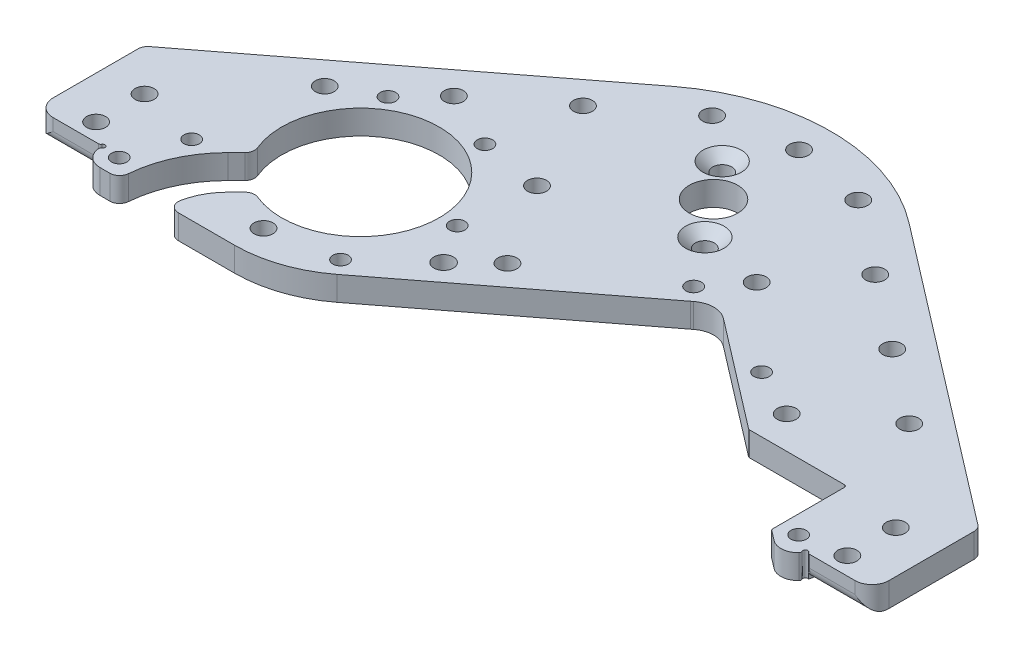
SolidWorks part; units mm, degrees
material "Alum Plate"
ref_plane "Front Plane" through (0, 0, 0) normal (0, 0, 1) x (1, 0, 0)
ref_plane "Top Plane" through (0, 0, 0) normal (0, 1, 0) x (1, 0, 0)
ref_plane "Right Plane" through (0, 0, 0) normal (1, 0, 0) x (0, 0, -1)
sketch "Top Layout" plane through (0, 0, 0) normal (0, 1, 0) x (1, 0, 0)
  line L0 (-114.046, -123.825) -> (-104.775, -123.825) construction
  line L1 (-104.775, -142.875) -> (-101.6, -142.875)
  line L2 (-104.775, -142.875) -> (-104.775, -104.775)
  line L3 (-104.775, -104.775) -> (-101.6, -104.775)
  line L4 (-101.6, -142.875) -> (-101.6, -104.775)
  line L5 (-104.775, -142.875) -> (-101.6, -104.775) construction
  line L6 (-104.775, -104.775) -> (-101.6, -142.875) construction
  line L7 (-19.05, -105.8164) -> (-101.6, -105.8164)
  line L8 (-19.05, -105.8164) -> (-19.05, -141.8336)
  line L9 (-19.05, -141.8336) -> (-101.6, -141.8336)
  line L10 (-101.6, -105.8164) -> (-101.6, -141.8336)
  line L11 (-19.05, -105.8164) -> (-101.6, -141.8336) construction
  line L12 (-19.05, -141.8336) -> (-101.6, -105.8164) construction
  line L13 (-133.096, -85.725) -> (-114.046, -85.725)
  line L14 (-133.096, -85.725) -> (-133.096, -161.925)
  line L15 (-133.096, -161.925) -> (-114.046, -161.925)
  line L16 (-114.046, -85.725) -> (-114.046, -161.925)
  line L17 (-133.096, -85.725) -> (-114.046, -161.925) construction
  line L18 (-133.096, -161.925) -> (-114.046, -85.725) construction
  line L19 (-104.775, -123.825) -> (0, -123.825) construction
  line L20 (0, -123.825) -> (0, 0) construction
  line L21 (-52.3528, -40.1717) -> (0, 0) construction
  line L22 (-70.6449, -16.3328) -> (-18.2922, 23.8388)
  line L23 (-34.0606, -64.0105) -> (18.2922, -23.8388)
  line L24 (-30.9251, 40.3023) -> (-122.2248, -29.7544)
  line L25 (-153.9748, -53.975) -> (-153.9748, -123.825)
  line L26 (-109.5248, -162.052) -> (109.5248, -162.052)
  line L27 (0, -162.052) -> (0, -123.825) construction
  line L28 (-109.5248, -162.052) -> (-109.5248, -20.0093) construction
  line L29 (-104.775, -142.875) -> (-104.775, -152.527)
  line L30 (-104.775, -152.527) -> (104.775, -152.527)
  line L31 (104.775, -104.775) -> (101.6, -104.775)
  line L32 (-144.4498, -73.025) -> (-109.5248, -73.025)
  line L33 (-144.4498, -73.025) -> (-144.4498, -123.825)
  line L34 (-144.4498, -123.825) -> (-109.5248, -123.825) construction
  line L35 (-109.5248, -73.025) -> (-109.5248, -162.052)
  line L36 (-144.4498, -73.025) -> (-109.5248, -123.825) construction
  line L37 (-144.4498, -123.825) -> (-109.5248, -73.025) construction
  line L38 (101.6, -142.875) -> (101.6, -104.775)
  line L39 (104.775, -142.875) -> (101.6, -142.875)
  line L40 (104.775, -142.875) -> (104.775, -104.775)
  line L41 (104.775, -142.875) -> (104.775, -152.527)
  line L42 (109.5248, -162.052) -> (109.5248, -20.0093) construction
  line L43 (30.9251, 40.3023) -> (122.2248, -29.7544)
  line L45 (19.05, -141.8336) -> (101.6, -141.8336)
  line L46 (101.6, -105.8164) -> (101.6, -141.8336)
  line L47 (19.05, -105.8164) -> (101.6, -105.8164)
  line L48 (19.05, -105.8164) -> (19.05, -141.8336)
  line L49 (133.096, -161.925) -> (114.046, -161.925)
  line L50 (114.046, -85.725) -> (114.046, -161.925)
  line L51 (133.096, -85.725) -> (114.046, -85.725)
  line L52 (133.096, -85.725) -> (133.096, -161.925)
  line L53 (144.4498, -123.825) -> (109.5248, -123.825) construction
  line L54 (109.5248, -73.025) -> (109.5248, -162.052)
  line L55 (144.4498, -73.025) -> (109.5248, -73.025)
  line L56 (144.4498, -73.025) -> (144.4498, -123.825)
  line L57 (-109.5248, -123.825) -> (-109.5248, -162.052) construction
  line L62 (-153.9748, -53.975) -> (-122.2248, -53.975)
  line L63 (-122.2248, -53.975) -> (-122.2248, -29.7544)
  line L64 (-144.4498, -123.825) -> (-153.9748, -123.825)
  line L65 (153.9748, -53.975) -> (153.9748, -123.825)
  line L66 (109.5248, -123.825) -> (109.5248, -162.052) construction
  line L67 (144.4498, -123.825) -> (153.9748, -123.825)
  line L68 (122.2248, -29.7544) -> (122.2248, -53.975)
  line L73 (-104.775, -104.775) -> (-104.775, -16.3647) construction
  line L74 (-95.25, -162.052) -> (-95.25, -9.0559) construction
  line L75 (-109.5248, -162.052) -> (-109.5248, -123.825) construction
  line L76 (109.5248, -162.052) -> (109.5248, -123.825) construction
  line L77 (122.2248, -53.975) -> (153.9748, -53.975)
  line L83 (104.775, -155.5496) -> (-104.775, -155.5496) construction
  line L88 (95.25, -162.052) -> (95.25, -9.0559) construction
  line L89 (104.775, -104.775) -> (104.775, -16.3647) construction
  line L92 (-104.775, -152.527) -> (-104.775, -162.052) construction
  line L93 (-14.605, -76.327) -> (14.605, -76.327)
  line L94 (-14.605, -76.327) -> (-14.605, -152.527)
  line L95 (-14.605, -152.527) -> (14.605, -152.527)
  line L96 (14.605, -76.327) -> (14.605, -152.527)
  line L97 (-14.605, -76.327) -> (14.605, -152.527) construction
  line L98 (-14.605, -152.527) -> (14.605, -76.327) construction
  line L99 (104.775, -152.527) -> (104.775, -162.052) construction
  line L100 (-19.05, -105.8164) -> (0, -105.8164) construction
  line L107 (0, -105.8164) -> (19.05, -105.8164) construction
  line L108 (104.775, -123.825) -> (114.046, -123.825) construction
  circle A0 centre (0, 0) radius 114.3
  circle A1 centre (0, 0) radius 6.35
  circle A2 centre (-52.3528, -40.1717) radius 17.8
  circle A3 centre (0, 0) radius 30.0482
  circle A4 centre (-52.3528, -40.1717) radius 30.0482
  arc A5 (-30.9251, 40.3023) -> (30.9251, 40.3023) centre (0, 0) cw
  point P2 (-103.1875, -123.825)
  point P7 (-60.325, -123.825)
  point P12 (-123.571, -123.825)
  point P30 (-126.9873, -98.425)
  point P35 (0, -114.427)
  point P53 (0, -152.527)
  dimension "D1" = 35.6
  dimension "D2" = 12.7
  dimension "D3" = 228.6
  dimension "D11" = 60.0964
  dimension "D12" = 50.8
  dimension "D14" = 52.5
  dimension "D4" = 3.175
  dimension "D5" = 19.05
  dimension "D6" = 76.2
  dimension "D7" = 82.55
  dimension "D8" = 38.1
  dimension "D9" = 104.775
  dimension "D10" = 18.0086
  dimension "D13" = 9.525
  dimension "D15" = 4.7498
  dimension "D16" = 9.525
  dimension "D17" = 9.652
  dimension "D18" = 50.8
  dimension "D19" = 12.446
  dimension "D20" = 65.9892
  dimension "D21" = 19.05
  dimension "D22" = 34.925
  dimension "D23" = 123.825
  dimension "D24" = 12.7
  dimension "D25" = 9.525
  dimension "D26" = 29.21
  dimension "D27" = 76.2
  dimension "D28" = 3.0226
sketch "Side Layout" plane through (0, 0, 0) normal (1, 0, 0) x (0, 0, -1)
  line L0 (0, -38.1) -> (0, 33.7344) construction
  line L1 (-114.3, -20.955) -> (114.3, -20.955)
  line L2 (-114.3, -20.955) -> (-114.3, -33.655)
  line L3 (-114.3, -33.655) -> (114.3, -33.655)
  line L4 (114.3, -20.955) -> (114.3, -33.655)
  line L5 (-114.3, -20.955) -> (114.3, -33.655) construction
  line L6 (-114.3, -33.655) -> (114.3, -20.955) construction
  line L7 (-9.525, -32.9406) -> (9.525, -32.9406)
  line L8 (-9.525, -32.9406) -> (-9.525, -38.1)
  line L9 (-9.525, -38.1) -> (9.525, -38.1)
  line L10 (9.525, -32.9406) -> (9.525, -38.1)
  line L11 (-9.525, -32.9406) -> (9.525, -38.1) construction
  line L12 (-9.525, -38.1) -> (9.525, -32.9406) construction
  line L13 (-11.9126, -29.3338) -> (11.9126, -29.3338)
  line L14 (-11.9126, -29.3338) -> (-11.9126, -32.9406)
  line L15 (-11.9126, -32.9406) -> (11.9126, -32.9406)
  line L16 (11.9126, -29.3338) -> (11.9126, -32.9406)
  line L17 (-11.9126, -29.3338) -> (11.9126, -32.9406) construction
  line L18 (-11.9126, -32.9406) -> (11.9126, -29.3338) construction
  line L19 (-6.35, -32.9406) -> (6.35, -32.9406)
  line L20 (-6.35, -32.9406) -> (-6.35, 33.7344)
  line L21 (-6.35, 33.7344) -> (6.35, 33.7344)
  line L22 (6.35, -32.9406) -> (6.35, 33.7344)
  line L23 (-6.35, -32.9406) -> (6.35, 33.7344) construction
  line L24 (-6.35, 33.7344) -> (6.35, -32.9406) construction
  line L25 (-162.052, 0) -> (-123.825, 0) construction
  line L26 (114.3, -33.655) -> (114.3, 0) construction
  line L27 (-142.875, 19.05) -> (-104.775, 19.05)
  line L28 (-40.1717, -9.525) -> (-40.1717, 5.4) construction
  line L29 (-142.875, 19.05) -> (-142.875, -19.05)
  line L30 (-142.875, -19.05) -> (-104.775, -19.05)
  line L31 (-104.775, 19.05) -> (-104.775, -19.05)
  line L32 (-142.875, 19.05) -> (-104.775, -19.05) construction
  line L33 (-142.875, -19.05) -> (-104.775, 19.05) construction
  line L34 (-130.175, -38.1) -> (-117.9516, -38.1) construction
  line L35 (-57.9717, -14.6) -> (-22.3717, -14.6)
  line L36 (-30.0482, -2.794) -> (30.0482, -2.794)
  line L37 (-30.0482, -2.794) -> (-30.0482, -20.955)
  line L38 (-30.0482, -20.955) -> (30.0482, -20.955)
  line L39 (30.0482, -2.794) -> (30.0482, -20.955)
  line L40 (-30.0482, -2.794) -> (30.0482, -20.955) construction
  line L41 (-30.0482, -20.955) -> (30.0482, -2.794) construction
  line L42 (-30.0482, -2.794) -> (-30.0482, 0) construction
  line L43 (-123.825, 0) -> (0, 0) construction
  line L44 (-57.9717, -14.6) -> (-57.9717, 25.4)
  line L45 (-57.9717, 25.4) -> (-22.3717, 25.4)
  line L46 (-22.3717, -14.6) -> (-22.3717, 25.4)
  line L47 (-19.05, 0) -> (19.05, 0)
  line L48 (-19.05, 0) -> (-19.05, -1.9812)
  line L49 (-19.05, -1.9812) -> (19.05, -1.9812)
  line L50 (19.05, 0) -> (19.05, -1.9812)
  line L51 (-19.05, 0) -> (19.05, -1.9812) construction
  line L52 (-19.05, -1.9812) -> (19.05, 0) construction
  line L53 (-70.2199, -3.175) -> (-10.1235, -3.175)
  line L54 (-70.2199, -3.175) -> (-70.2199, -15.875)
  line L55 (-70.2199, -15.875) -> (-10.1235, -15.875)
  line L56 (-10.1235, -3.175) -> (-10.1235, -15.875)
  line L57 (-70.2199, -3.175) -> (-10.1235, -15.875) construction
  line L58 (-70.2199, -15.875) -> (-10.1235, -3.175) construction
  line L59 (-40.1717, -9.525) -> (-40.1717, 0) construction
  line L60 (-57.9717, -14.6) -> (-22.3717, 25.4) construction
  line L61 (-57.9717, 25.4) -> (-22.3717, -14.6) construction
  line L62 (-22.3717, 0) -> (-57.9717, 0) construction
  line L63 (-137.8162, 0) -> (-123.825, -13.9912) construction
  line L64 (-139.065, 15.24) -> (-108.585, 15.24) construction
  line L65 (-139.065, 15.24) -> (-139.065, -15.24) construction
  line L66 (-139.065, -15.24) -> (-108.585, -15.24) construction
  line L67 (-108.585, 15.24) -> (-108.585, -15.24) construction
  line L68 (-139.065, 15.24) -> (-108.585, -15.24) construction
  line L69 (-139.065, -15.24) -> (-108.585, 15.24) construction
  line L70 (-137.8162, 0) -> (-123.825, 13.9912) construction
  line L71 (-123.825, -13.9912) -> (-109.8338, 0) construction
  line L72 (-123.825, 13.9912) -> (-109.8338, 0) construction
  line L73 (-137.8162, 0) -> (-109.8338, 0) construction
  line L74 (-123.825, -13.9912) -> (-123.825, 13.9912) construction
  line L75 (-6.35, 17.8594) -> (6.35, 17.8594)
  line L76 (114.3, 0) -> (-114.3, 0) construction
  line L77 (-22.3717, 19.05) -> (-6.35, 19.05) construction
  line L78 (-123.825, 38.1) -> (-97.9206, 38.1) construction
  line L79 (-19.05, -3.5814) -> (19.05, -3.5814)
  line L80 (-19.05, -3.5814) -> (-19.05, -1.9812)
  line L81 (-19.05, -1.9812) -> (19.05, -1.9812)
  line L82 (19.05, -3.5814) -> (19.05, -1.9812)
  line L83 (-19.05, -3.5814) -> (19.05, -1.9812) construction
  line L84 (-19.05, -1.9812) -> (19.05, -3.5814) construction
  line L85 (-8.7376, -16.7608) -> (8.7376, -16.7608)
  line L86 (-8.7376, -16.7608) -> (-8.7376, -29.3338)
  line L87 (-8.7376, -29.3338) -> (8.7376, -29.3338)
  line L88 (8.7376, -16.7608) -> (8.7376, -29.3338)
  line L89 (-8.7376, -16.7608) -> (8.7376, -29.3338) construction
  line L90 (-8.7376, -29.3338) -> (8.7376, -16.7608) construction
  line L91 (-8.7376, -3.5814) -> (8.7376, -3.5814)
  line L92 (-8.7376, -3.5814) -> (-8.7376, -16.1544)
  line L93 (-8.7376, -16.1544) -> (8.7376, -16.1544)
  line L94 (8.7376, -3.5814) -> (8.7376, -16.1544)
  line L95 (-8.7376, -3.5814) -> (8.7376, -16.1544) construction
  line L96 (-8.7376, -16.1544) -> (8.7376, -3.5814) construction
  circle A0 centre (-123.825, 0) radius 18.0086
  circle A1 centre (-123.825, 0) radius 38.1
  circle A2 centre (-139.065, 15.24) radius 1.905
  circle A3 centre (-108.585, 15.24) radius 1.905
  circle A4 centre (-108.585, -15.24) radius 1.905
  circle A5 centre (-139.065, -15.24) radius 1.905
  circle A6 centre (-137.8162, 0) radius 1.6002
  circle A7 centre (-123.825, 13.9912) radius 1.6002
  circle A8 centre (-109.8338, 0) radius 1.6002
  circle A9 centre (-123.825, -13.9912) radius 1.6002
  point P0 (0, -27.305)
  point P6 (0, -31.1372)
  point P7 (0, -35.5203)
  point P21 (0, 0.3969)
  point P32 (0, -11.8745)
  point P43 (0, -0.9906)
  point P55 (-40.1717, -9.525)
  point P72 (-40.1717, 5.4)
  point P88 (0, -23.0473)
  point P93 (0, -2.7813)
  point P102 (0, -9.8679)
  dimension "D17" = 3.81
  dimension "D18" = 3.2004
  dimension "D1" = 12.7
  dimension "D2" = 5.1594
  dimension "D3" = 19.05
  dimension "D4" = 3.6068
  dimension "D5" = 23.8252
  dimension "D6" = 12.7
  dimension "D7" = 18.161
  dimension "D8" = 1.9812
  dimension "D9" = 12.7
  dimension "D10" = 40
  dimension "D11" = 25.4
  dimension "D12" = 50.8
  dimension "D13" = 41.275
  dimension "D14" = 30.48
  dimension "D15" = 4.445
  dimension "D16" = 19.7866
  dimension "D19" = 15.875
  dimension "D20" = 6.35
  dimension "D21" = 38.1
  dimension "D22" = 1.6002
  dimension "D23" = 38.1
  dimension "D24" = 17.4752
  dimension "D25" = 12.573
ref_plane "Plane1" through (0, 25.4, 0) normal (0, 1, 0) x (1, 0, 0)
sketch "Sketch3" plane through (0, 25.4, 0) normal (0, 1, 0) x (1, 0, 0)
  line L0 (-104.775, -36.3747) -> (-30.9251, 20.2924)
  line L1 (-104.775, -104.775) -> (-104.775, -16.3647) construction
  line L2 (0, -200130.175) -> (0, 199882.0484) construction
  line L3 (-30.9251, 40.3023) -> (-122.2248, -29.7544) construction
  line L5 (-104.775, -36.3747) -> (-104.775, -77.6497)
  line L6 (-92.075, -77.6497) -> (-104.775, -77.6497)
  line L7 (30.9251, 20.2924) -> (104.775, -36.3747)
  line L8 (104.775, -77.6497) -> (92.075, -77.6497)
  line L9 (104.775, -36.3747) -> (104.775, -77.6497)
  line L11 (104.775, -104.775) -> (104.775, -16.3647) construction
  line L12 (30.9251, 40.3023) -> (122.2248, -29.7544) construction
  line L13 (92.075, -74.6536) -> (24.1423, -22.5271)
  line L14 (-32.2514, -66.3682) -> (20.1013, -26.1965)
  line L15 (-30.9251, 20.2924) -> (0, 44.022)
  line L16 (0, 44.022) -> (30.9251, 20.2924)
  line L17 (-92.075, -77.6497) -> (-92.075, -73.1917)
  line L19 (-92.075, -73.1917) -> (-52.3528, -73.1917)
  line L20 (92.075, -74.6536) -> (92.075, -77.6497)
  circle A1 centre (-52.3528, -40.1717) radius 20.6375
  circle A2 centre (0, 0) radius 6.35
  circle A3 centre (0, 0) radius 6.35 construction
  arc A4 (-52.3528, -73.1917) -> (-32.2514, -66.3682) centre (-52.3528, -40.1717) ccw
  arc A5 (20.1013, -26.1965) -> (24.1423, -22.5271) centre (0, 0) ccw
  arc A6 (30.9251, 20.2924) -> (-30.9251, 20.2924) centre (0, -20.01) ccw construction
  point P28 (0, 44.022)
  dimension "D1" = 33.02
  dimension "D5" = 50.8
  dimension "D7" = 41.275
  dimension "D2" = 41.275
  dimension "D3" = 34.925
  dimension "D4" = 12.7
  dimension "D6" = 38.1
extrude "Boss-Extrude1" add sketch "Sketch3" against normal blind 6.35
ref_plane "Plane3" through (-104.775, 0, 0) normal (-1, 0, 0) x (0, 0, 1)
sketch "Sketch6" plane through (-104.775, 0, 0) normal (-1, 0, 0) x (0, 0, 1)
  line L0 (162.052, -25.4) -> (162.052, 25.4)
  line L1 (162.052, 25.4) -> (77.6497, 25.4)
  line L2 (36.3747, 25.4) -> (77.6497, 25.4) construction
  line L3 (147.7645, 11.1125) -> (162.052, 11.1125) construction
  line L4 (162.052, 0) -> (71.2997, 0) construction
  line L5 (77.6497, 25.4) -> (77.6497, 19.05)
  line L6 (77.6497, 19.05) -> (36.3747, 19.05)
  line L7 (36.3747, 19.05) -> (36.3747, 6.35)
  line L8 (36.3747, 6.35) -> (71.2997, 6.35)
  line L10 (99.6315, -3.175) -> (99.6315, 11.1125) construction
  line L11 (71.2997, -25.4) -> (162.052, -25.4)
  line L13 (71.2997, 6.35) -> (71.2997, -25.4)
  line L14 (152.527, -25.4) -> (152.527, 25.4) construction
  line L15 (99.6315, 11.1125) -> (99.6315, 25.4) construction
  line L16 (147.7645, 11.1125) -> (147.7645, 25.4) construction
  line L17 (94.869, -7.9375) -> (104.394, -7.9375) construction
  line L18 (94.869, -7.9375) -> (94.869, 25.4) construction
  line L19 (94.869, 25.4) -> (104.394, 25.4) construction
  line L20 (104.394, -7.9375) -> (104.394, 25.4) construction
  line L21 (94.869, -7.9375) -> (104.394, 25.4) construction
  line L22 (94.869, 25.4) -> (104.394, -7.9375) construction
  line L23 (147.7645, 11.1125) -> (147.7645, -3.175) construction
  line L24 (104.394, -7.9375) -> (123.825, -7.9375) construction
  line L25 (143.002, -7.9375) -> (152.527, -7.9375) construction
  line L26 (143.002, -7.9375) -> (143.002, 25.4) construction
  line L27 (143.002, 25.4) -> (152.527, 25.4) construction
  line L28 (152.527, -7.9375) -> (152.527, 25.4) construction
  line L29 (143.002, -7.9375) -> (152.527, 25.4) construction
  line L30 (143.002, 25.4) -> (152.527, -7.9375) construction
  line L31 (123.825, -7.9375) -> (152.527, -7.9375) construction
  line L32 (104.775, 19.05) -> (104.775, -19.05) construction
  line L34 (155.702, -25.4) -> (155.702, 25.4) construction
  circle A0 centre (109.8338, 0) radius 1.6002 construction
  circle A1 centre (123.825, 13.9912) radius 1.6002 construction
  circle A2 centre (137.8162, 0) radius 1.6002 construction
  circle A3 centre (123.825, -13.9912) radius 1.6002 construction
  circle A4 centre (109.8338, 0) radius 1.6002 construction
  circle A5 centre (123.825, 13.9912) radius 1.6002 construction
  circle A6 centre (137.8162, 0) radius 1.6002 construction
  circle A7 centre (123.825, -13.9912) radius 1.6002 construction
  circle A8 centre (123.825, 0) radius 18.0086 construction
  circle A9 centre (123.825, 0) radius 18.0086 construction
  circle A10 centre (123.825, 0) radius 9.525
  circle A11 centre (108.585, -15.24) radius 1.905 construction
  circle A12 centre (108.585, 15.24) radius 1.905 construction
  circle A13 centre (139.065, 15.24) radius 1.905 construction
  circle A14 centre (139.065, -15.24) radius 1.905 construction
  circle A15 centre (108.585, -15.24) radius 1.905
  circle A16 centre (108.585, 15.24) radius 1.905
  circle A17 centre (139.065, 15.24) radius 1.905
  circle A18 centre (139.065, -15.24) radius 1.905
  circle A19 centre (147.7645, 11.1125) radius 2.5527
  circle A26 centre (99.6315, 11.1125) radius 2.5527
  circle A27 centre (99.6315, -3.175) radius 2.5527
  circle A28 centre (147.7645, -3.175) radius 2.5527
  point P29 (0, 0)
  point P55 (99.6315, 8.7312)
  point P61 (147.7645, 8.7312)
  dimension "D4" = 19.05
  dimension "D7" = 5.1054
  dimension "D1" = 6.35
  dimension "D2" = 12.7
  dimension "D3" = 25.4
  dimension "D5" = 6.35
  dimension "D6" = 3.175
  dimension "D8" = 0.381
  dimension "D9" = 14.2875
  dimension "D10" = 9.525
  dimension "D12" = 33.3375
sketch "Sketch12" [suppressed] plane through (0, 19.05, 0) normal (0, 1, 0) x (1, 0, 0)
  line L0 (-104.775, -77.6497) -> (-104.775, -36.3747)
  line L1 (-104.775, -36.3747) -> (-92.075, -36.3747)
  line L3 (-92.075, -36.3747) -> (-92.075, -77.6497)
  line L5 (-92.075, -77.6497) -> (-104.775, -77.6497)
  line L6 (-98.425, -77.6497) -> (-98.425, -63.3622) construction
  line L7 (-98.425, -63.3622) -> (-98.425, -50.6622) construction
  line L8 (-98.425, -50.6622) -> (-98.425, -36.3747) construction
  line L10 (-98.425, -36.3747) -> (-104.775, -36.3747) construction
  circle A0 centre (-98.425, -63.3622) radius 2.5527
  circle A1 centre (-98.425, -50.6622) radius 2.5527
  dimension "D2" = 5.1054
  dimension "D1" = 12.7
  dimension "D3" = 12.7
sketch "Sketch8" plane through (0, 25.4, 0) normal (0, 1, 0) x (1, 0, 0)
  line L0 (-109.5248, -162.052) -> (-109.5248, -20.0093) construction
  line L1 (-104.775, -77.6497) -> (-109.5248, -77.6497)
  line L2 (-104.775, -77.6497) -> (-104.775, -36.3747)
  line L3 (-104.775, -36.3747) -> (-109.5248, -36.3747)
  line L4 (-109.5248, -77.6497) -> (-109.5248, -36.3747)
  line L5 (-104.775, -77.6497) -> (-109.5248, -36.3747) construction
  line L6 (-104.775, -36.3747) -> (-109.5248, -77.6497) construction
  line L7 (104.775, -77.6497) -> (109.5248, -77.6497)
  line L8 (104.775, -77.6497) -> (104.775, -36.3747)
  line L9 (104.775, -36.3747) -> (109.5248, -36.3747)
  line L10 (109.5248, -77.6497) -> (109.5248, -36.3747)
  line L11 (104.775, -77.6497) -> (109.5248, -36.3747) construction
  line L12 (104.775, -36.3747) -> (109.5248, -77.6497) construction
  point P4 (-107.1499, -57.0122)
  point P10 (107.1499, -57.0122)
extrude "Boss-Extrude4" add sketch "Sketch8" against normal through all
sketch "Sketch9" plane through (0, 25.4, 0) normal (0, 1, 0) x (1, 0, 0)
  line L0 (7.4916, -9.7632) -> (0, 0) construction
  line L1 (0, 0) -> (-7.4916, 9.7632) construction
  line L2 (0, 44.022) -> (-104.775, -36.3747) construction
  circle A0 centre (-7.4916, 9.7632) radius 2.4892
  circle A1 centre (7.4916, -9.7632) radius 2.4892
  dimension "D2" = 4.9784
  dimension "D1" = 24.6126
extrude "Collar Holes" cut sketch "Sketch9" against normal through all
sketch "Sketch10" plane through (0, 25.4, 0) normal (0, 1, 0) x (1, 0, 0)
  line L0 (0, 33.4567) -> (0, 30.79) construction
  line L1 (-5.1026, 40.1066) -> (0, 33.4567) construction
  line L2 (0, 33.4567) -> (5.1026, 40.1066) construction
  line L3 (0, 44.022) -> (-104.775, -36.3747) construction
  line L4 (104.775, -36.3747) -> (0, 44.022) construction
  circle A0 centre (0, 33.4567) radius 4.7625 construction
  circle A1 centre (0, 33.4567) radius 2.0193
  arc A3 (30.9251, 20.2924) -> (-30.9251, 20.2924) centre (0, -20.01) ccw construction
  dimension "D2" = 9.525
  dimension "D3" = 4.0386
  dimension "D1" = 8.382
extrude "Spacer Holes" cut sketch "Sketch10" against normal through all
pattern_linear "Spacer Hole Pattern" count 5 spacing 24.13 along (-0.7934, 0, 0.6088) of "Spacer Holes"
mirror "Spacer Hole Mirror" about plane through (0, 0, 0) normal (1, 0, 0) of "Spacer Hole Pattern"
sketch "Sketch16" plane through (0, 25.4, 0) normal (0, 1, 0) x (1, 0, 0)
  line L0 (-109.5248, -50.6622) -> (-98.425, -50.6622) construction
  line L1 (-109.5248, -36.3747) -> (-109.5248, -77.6497) construction
  line L2 (-98.425, -50.6622) -> (-98.425, -63.3622) construction
  line L3 (-98.425, -63.3622) -> (-109.5248, -63.3622) construction
  line L4 (-98.425, -63.3622) -> (-98.425, -77.6497) construction
  line L5 (-109.5248, -77.6497) -> (-92.075, -77.6497) construction
  line L6 (-98.425, -50.6622) -> (-98.425, -36.3747) construction
  line L7 (-104.775, -36.3747) -> (-109.5248, -36.3747) construction
  line L8 (-104.775, -36.3747) -> (-104.775, -77.6497) construction
  line L9 (0, 0) -> (0, 30.79) construction
  line L10 (104.775, -36.3747) -> (104.775, -77.6497) construction
  circle A0 centre (-98.425, -50.6622) radius 2.0193
  circle A1 centre (-98.425, -63.3622) radius 2.0193
  circle A4 centre (98.425, -63.3622) radius 2.0193
  circle A5 centre (98.425, -50.6622) radius 2.0193
  arc A6 (30.9251, 20.2924) -> (-30.9251, 20.2924) centre (0, -20.01) ccw construction
  dimension "D1" = 4.0386
  dimension "D2" = 12.7
  dimension "D3" = 6.35
extrude "Custom Nutstrip Holes" cut sketch "Sketch16" against normal through all
sketch "Sketch36" plane through (0, 25.4, 0) normal (0, 1, 0) x (1, 0, 0)
  line L0 (-52.3528, -65.5717) -> (-12.44, -41.5615) construction
  line L1 (-12.44, -41.5615) -> (24.5129, -13.2066) construction
  line L2 (24.5129, -13.2066) -> (58.2939, -39.1277) construction
  line L3 (-32.2514, -66.3682) -> (20.1013, -26.1965) construction
  line L4 (24.1423, -22.5271) -> (92.075, -74.6536) construction
  line L5 (-12.44, -41.5615) -> (-7.8012, -47.6069) construction
  line L6 (58.2939, -39.1277) -> (53.6552, -45.1731) construction
  line L7 (-52.3528, -65.5717) -> (-52.3528, -40.1717) construction
  line L8 (58.2939, -39.1277) -> (92.075, -65.0488) construction
  line L9 (92.075, -65.0488) -> (92.075, -77.6497) construction
  line L10 (-52.3528, -40.1717) -> (-26.1764, -20.0858) construction
  line L11 (-26.1764, -20.0858) -> (0, 0) construction
  line L12 (92.075, -74.6536) -> (92.075, -77.6497) construction
  circle A0 centre (-52.3528, -65.5717) radius 2.0193
  circle A1 centre (58.2939, -39.1277) radius 2.0193
  circle A2 centre (24.5129, -13.2066) radius 2.0193
  circle A3 centre (-12.44, -41.5615) radius 2.0193
  circle A4 centre (-76.5745, -25.3009) radius 2.0193 construction
  circle A5 centre (-52.3528, -65.5717) radius 4.7625 construction
  circle A6 centre (-12.44, -41.5615) radius 4.7625 construction
  circle A7 centre (24.5129, -13.2066) radius 4.7625 construction
  circle A8 centre (58.2939, -39.1277) radius 4.7625 construction
  arc A9 (-52.3528, -73.1917) -> (-32.2514, -66.3682) centre (-52.3528, -40.1717) ccw construction
  circle A10 centre (-26.1764, -20.0858) radius 2.0193
  dimension "D1" = 9.525
  dimension "D2" = 25.4
  dimension "D3" = 7.62
extrude "Aux Spacer Holes" cut sketch "Sketch36" against normal through all
sketch "Sketch38" [suppressed] plane through (-104.775, 0, 0) normal (-1, 0, 0) x (0, 0, 1)
  line L1 (152.527, -7.9375) -> (143.002, -7.9375)
  line L2 (152.527, -7.9375) -> (152.527, 25.4)
  line L3 (152.527, 25.4) -> (143.002, 25.4)
  line L4 (143.002, -7.9375) -> (143.002, 25.4)
  line L5 (152.527, -7.9375) -> (143.002, 25.4) construction
  line L6 (152.527, 25.4) -> (143.002, -7.9375) construction
  point P4 (147.7645, 8.7312)
extrude "Cut-Extrude16" [suppressed] cut sketch "Sketch38" against normal blind 9.525
sketch "Sketch46" [suppressed] plane through (-104.775, 0, 0) normal (-1, 0, 0) x (0, 0, 1)
  line L0 (142.875, 19.05) -> (104.775, -19.05) construction
  line L1 (104.14, 19.685) -> (143.51, 19.685)
  line L2 (104.14, 19.685) -> (104.14, -19.685)
  line L3 (104.14, -19.685) -> (143.51, -19.685)
  line L4 (143.51, 19.685) -> (143.51, -19.685)
  line L5 (104.14, 19.685) -> (143.51, -19.685) construction
  line L6 (104.14, -19.685) -> (143.51, 19.685) construction
  point P0 (123.825, 0)
  dimension "D1" = 39.37
extrude "Cut-Extrude21" [suppressed] cut sketch "Sketch46" against normal blind 6.985
ref_plane "Plane5" through (0, 0, 152.527) normal (0, 0, 1) x (1, 0, 0)
sketch "Sketch41" plane through (0, 0, 152.527) normal (0, 0, 1) x (1, 0, 0)
  line L0 (-104.775, -7.9375) -> (-104.775, 25.4) construction
  line L1 (-104.775, -7.9375) -> (-104.775, 12.7)
  line L2 (-104.775, -7.9375) -> (104.775, -7.9375)
  line L3 (104.775, -7.9375) -> (104.775, 12.7)
  line L4 (104.775, 25.4) -> (-104.775, 25.4)
  line L5 (0, -7.9375) -> (0, 25.4) construction
  line L6 (-104.775, 3.9624) -> (-100.0125, 3.9624) construction
  line L7 (-100.0125, 3.9624) -> (-100.0125, 25.4) construction
  line L8 (104.775, 3.9624) -> (100.0125, 3.9624) construction
  line L9 (100.0125, 3.9624) -> (100.0125, 25.4) construction
  line L10 (19.05, 20.6375) -> (23.8252, 20.6375) construction
  line L11 (19.05, 15.875) -> (78.5876, 15.875) construction
  line L12 (19.05, 15.875) -> (19.05, 25.4) construction
  line L13 (19.05, 25.4) -> (78.5876, 25.4) construction
  line L14 (78.5876, 15.875) -> (78.5876, 25.4) construction
  line L15 (19.05, 15.875) -> (78.5876, 25.4) construction
  line L16 (19.05, 25.4) -> (78.5876, 15.875) construction
  line L17 (23.8252, 20.6375) -> (38.1127, 20.6375) construction
  line L18 (38.1127, 20.6375) -> (52.4002, 20.6375) construction
  line L19 (52.4002, 20.6375) -> (66.6877, 20.6375) construction
  line L20 (-104.775, 25.4) -> (-112.395, 25.4)
  line L21 (-112.395, 25.4) -> (-112.395, 3.175)
  line L22 (-112.395, 3.175) -> (-109.5248, 3.175)
  line L23 (-109.5248, 3.175) -> (-109.5248, 12.7)
  line L24 (-109.5248, 12.7) -> (-104.775, 12.7)
  line L25 (-104.775, 12.7) -> (-104.775, 25.4) construction
  line L26 (104.775, 25.4) -> (112.395, 25.4)
  line L27 (112.395, 25.4) -> (112.395, 3.175)
  line L28 (112.395, 3.175) -> (109.5248, 3.175)
  line L29 (109.5248, 3.175) -> (109.5248, 12.7)
  line L30 (109.5248, 12.7) -> (104.775, 12.7)
  line L31 (104.775, 12.7) -> (104.775, 25.4) construction
  line L32 (-100.0125, 3.9624) -> (-87.3125, 3.9624) construction
  line L33 (-63.5, -1.5875) -> (0, -1.5875) construction
  line L34 (0, -1.5875) -> (63.5, -1.5875) construction
  line L35 (63.5, -1.5875) -> (63.5, -7.9375) construction
  circle A0 centre (-100.0125, 3.9624) radius 2.5527
  circle A1 centre (100.0125, 3.9624) radius 2.5527
  circle A2 centre (23.8252, 20.6375) radius 2.5527
  circle A3 centre (38.1127, 20.6375) radius 2.5527
  circle A4 centre (52.4002, 20.6375) radius 2.5527
  circle A5 centre (66.6877, 20.6375) radius 2.5527
  circle A6 centre (-66.6877, 20.6375) radius 2.5527
  circle A7 centre (-52.4002, 20.6375) radius 2.5527
  circle A8 centre (-38.1127, 20.6375) radius 2.5527
  circle A9 centre (-23.8252, 20.6375) radius 2.5527
  circle A10 centre (-87.3125, 3.9624) radius 2.5527
  circle A11 centre (87.3125, 3.9624) radius 2.5527
  circle A12 centre (-63.5, -1.5875) radius 2.5527
  circle A13 centre (63.5, -1.5875) radius 2.5527
  point P14 (48.8188, 20.6375)
  dimension "D3" = 5.1054
  dimension "D7" = 5.1054
  dimension "D1" = 21.4376
  dimension "D2" = 4.7625
  dimension "D4" = 9.525
  dimension "D5" = 59.5376
  dimension "D6" = 4.7752
  dimension "D8" = 14.2875
  dimension "D9" = 7.62
  dimension "D10" = 4.7498
  dimension "D11" = 12.7
  dimension "D12" = 9.525
  dimension "D13" = 19.05
  dimension "D14" = 12.7
  dimension "D15" = 6.35
  dimension "D16" = 63.5
sketch "Sketch43" [suppressed] plane through (-109.5248, 0, 0) normal (-1, 0, 0) x (0, 0, 1)
  line L1 (152.527, 12.7) -> (155.702, 12.7)
  line L2 (152.527, 12.7) -> (152.527, 25.4)
  line L3 (152.527, 25.4) -> (155.702, 25.4)
  line L4 (155.702, 12.7) -> (155.702, 25.4)
  line L5 (152.527, 12.7) -> (155.702, 25.4) construction
  line L6 (152.527, 25.4) -> (155.702, 12.7) construction
  line L7 (162.052, 25.4) -> (77.6497, 25.4) construction
  point P4 (154.1145, 19.05)
  dimension "D1" = 3.175
sketch "Sketch44" plane through (0, 25.4, 0) normal (0, 1, 0) x (1, 0, 0)
  line L0 (73.8315, -147.7645) -> (73.8315, -152.527) construction
  line L1 (92.075, -74.6536) -> (92.075, -77.6497) construction
  line L2 (-92.075, -77.6497) -> (-92.075, -73.1917) construction
  line L3 (0, -123.825) -> (0, 0) construction
  line L4 (-92.075, -73.1917) -> (-52.3528, -73.1917) construction
  line L5 (-104.775, -104.775) -> (-104.775, -16.3647) construction
  line L6 (-32.2514, -66.3682) -> (20.1013, -26.1965) construction
  line L21 (-104.775, -68.1247) -> (-104.775, -152.527)
  line L22 (-104.775, -152.527) -> (104.775, -152.527)
  line L23 (104.775, -152.527) -> (104.775, -68.1247)
  line L34 (-104.775, -99.6315) -> (-100.0125, -99.6315) construction
  line L35 (-104.775, -147.7645) -> (-100.0125, -147.7645) construction
  line L36 (0, -152.527) -> (0, -35.6178) construction
  line L38 (30.969, -147.7645) -> (45.2565, -147.7645) construction
  line L39 (45.2565, -147.7645) -> (59.544, -147.7645) construction
  line L40 (59.544, -147.7645) -> (73.8315, -147.7645) construction
  line L41 (23.8252, -152.527) -> (30.969, -152.527) construction
  line L42 (104.775, -152.527) -> (-104.775, -152.527) construction
  line L43 (30.969, -152.527) -> (38.1127, -152.527) construction
  line L44 (30.969, -152.527) -> (30.969, -147.7645) construction
  line L45 (-92.075, -77.6497) -> (-104.775, -77.6497) construction
  line L48 (-35.1507, -62.5899) -> (-8.9743, -42.504) construction
  line L49 (-8.9743, -42.504) -> (17.2021, -22.4182) construction
  line L50 (45.5313, -32.9364) -> (87.3125, -64.9962) construction
  line L51 (92.075, -74.6536) -> (24.1423, -22.5271) construction
  line L52 (104.775, -77.6497) -> (92.075, -77.6497) construction
  line L79 (-104.775, -68.1247) -> (-92.075, -68.1247)
  line L80 (-92.075, -68.1247) -> (-92.075, -63.6667)
  line L85 (21.8118, -8.7328) -> (92.075, -62.6476)
  line L86 (-38.0499, -58.8115) -> (14.3028, -18.6398)
  line L87 (-92.075, -63.6667) -> (-52.3528, -63.6667)
  line L88 (92.075, -62.6476) -> (92.075, -68.1247)
  line L89 (92.075, -68.1247) -> (104.775, -68.1247)
  circle A0 centre (-73.8315, -147.7645) radius 2.5527
  circle A1 centre (-59.544, -147.7645) radius 2.5527
  circle A2 centre (-45.2565, -147.7645) radius 2.5527
  circle A3 centre (-30.969, -147.7645) radius 2.5527
  circle A17 centre (-100.0125, -99.6315) radius 2.5527
  circle A18 centre (-100.0125, -147.7645) radius 2.5527
  circle A19 centre (100.0125, -147.7645) radius 2.5527
  circle A20 centre (100.0125, -99.6315) radius 2.5527
  circle A21 centre (30.969, -147.7645) radius 2.5527
  circle A22 centre (45.2565, -147.7645) radius 2.5527
  circle A23 centre (59.544, -147.7645) radius 2.5527
  circle A24 centre (73.8315, -147.7645) radius 2.5527
  circle A25 centre (-87.3125, -68.4292) radius 4.7625 construction
  circle A26 centre (-35.1507, -62.5899) radius 4.7625 construction
  circle A27 centre (-8.9743, -42.504) radius 4.7625 construction
  circle A28 centre (17.2021, -22.4182) radius 4.7625 construction
  circle A29 centre (45.5313, -32.9364) radius 4.7625 construction
  circle A30 centre (87.3125, -64.9962) radius 4.7625 construction
  circle A32 centre (-87.3125, -68.4292) radius 2.5527
  circle A33 centre (-35.1507, -62.5899) radius 2.5527
  circle A34 centre (-8.9743, -42.504) radius 2.5527 construction
  circle A35 centre (17.2021, -22.4182) radius 2.5527
  circle A36 centre (45.5313, -32.9364) radius 2.5527
  circle A37 centre (87.3125, -64.9962) radius 2.5527
  circle A38 centre (-97.155, -85.2697) radius 7.62 construction
  circle A39 centre (97.155, -85.2697) radius 7.62 construction
  circle A40 centre (24.5121, -32.4156) radius 7.62 construction
  arc A41 (20.1013, -26.1965) -> (24.1423, -22.5271) centre (0, 0) ccw construction
  circle A42 centre (-97.155, -85.2697) radius 2.5527
  circle A43 centre (24.5121, -32.4156) radius 2.5527
  circle A44 centre (97.155, -85.2697) radius 2.5527
  arc A56 (14.3028, -18.6398) -> (21.8118, -8.7328) centre (0, 0) ccw
  arc A57 (-52.3528, -63.6667) -> (-38.0499, -58.8115) centre (-52.3528, -40.1717) ccw
  point P4 (-104.775, -152.527)
  dimension "D2" = 5.1054
  dimension "D7" = 5.1054
  dimension "D8" = 15.24
  dimension "D3" = 9.525
  dimension "D9" = 9.525
  dimension "D4" = 4.7625
  dimension "D5" = 14.2875
  dimension "D6" = 9.525
  dimension "D1" = 4.7625
  dimension "D10" = 52.664
sketch "Sketch82" [suppressed] plane through (0, 28.829, 0) normal (0, 1, 0) x (1, 0, 0)
  line L0 (-52.3528, -63.6667) -> (-92.075, -63.6667) construction
  line L1 (-52.3528, -65.5717) -> (-52.3528, -63.6667) construction
  line L2 (-12.4467, -41.5667) -> (-13.6064, -40.0553) construction
  line L3 (14.3028, -18.6398) -> (-38.0499, -58.8115) construction
  line L4 (24.5175, -13.2101) -> (25.6772, -11.6988) construction
  line L5 (92.075, -62.6476) -> (21.8118, -8.7328) construction
  line L6 (58.2962, -39.1295) -> (59.4559, -37.6181) construction
  line L7 (21.4643, -9.5551) -> (21.8118, -8.7328)
  line L8 (21.8118, -8.7328) -> (22.2143, -9.0416)
  circle A0 centre (-52.3528, -65.5717) radius 4.7625
  circle A1 centre (-12.4467, -41.5667) radius 4.7625
  arc A2 (21.4643, -9.5551) -> (22.2143, -9.0416) centre (24.5175, -13.2101) ccw
  circle A3 centre (58.2962, -39.1295) radius 4.7625
  arc A4 (14.3028, -18.6398) -> (21.8118, -8.7328) centre (0, 0) ccw construction
  dimension "D1" = 9.525
  dimension "D2" = 1.905
  dimension "D3" = 30.8104
  dimension "D4" = 83.6926
  dimension "D5" = 41.1154
extrude "Cut-Extrude38" [suppressed] cut sketch "Sketch82" against normal up to surface (3.429 mm away)
sketch "Sketch45" [suppressed] plane through (0, -25.4, 0) normal (0, -1, 0) x (1, 0, 0)
  circle A2 centre (24.5121, 32.4156) radius 6.35
  circle A4 centre (-97.155, 85.2697) radius 6.35
  circle A5 centre (97.155, 85.2697) radius 6.35
  dimension "D1" = 12.7
ref_plane "Plane6" through (0, 19.05, 0) normal (0, 1, 0) x (1, 0, 0)
sketch "Sketch59" [suppressed] plane through (0, 19.05, 0) normal (0, 1, 0) x (1, 0, 0)
  line L0 (0, 22.408) -> (0, 30.79) construction
  line L1 (-19.1436, 18.7673) -> (-24.2463, 25.4172) construction
  line L2 (0, 33.4567) -> (-5.1026, 40.1066) construction
  line L3 (-5.1026, 40.1066) -> (-24.2463, 25.4172) construction
  line L4 (-104.775, -36.3747) -> (-30.9251, 20.2924) construction
  line L5 (-19.1436, 18.7673) -> (0, 33.4567) construction
  circle A0 centre (0, 22.408) radius 4.7625
  circle A2 centre (-19.1436, 18.7673) radius 4.7625
  arc A3 (30.9251, 20.2924) -> (-30.9251, 20.2924) centre (0, -20.01) ccw construction
  dimension "D3" = 9.525
  dimension "D1" = 8.382
  dimension "D2" = 24.13
sketch "Sketch47" plane through (0, 25.4, 0) normal (0, 1, 0) x (1, 0, 0)
  line L0 (-21.3485, -42.7945) -> (-23.7291, -44.6212) construction
  line L1 (-81.9672, -61.1267) -> (-75.3534, -61.1267) construction
  line L2 (-19.1436, 18.7673) -> (-38.2872, 4.0779) construction
  line L3 (-38.2872, 4.0779) -> (-57.4308, -10.6115) construction
  line L4 (-57.4308, -10.6115) -> (-76.5745, -25.3009) construction
  line L5 (-19.1436, 18.7673) -> (0, 33.4567) construction
  line L6 (-76.5745, -25.3009) -> (-65.8758, -19.4248) construction
  line L7 (-65.8758, -19.4248) -> (-57.4308, -10.6115) construction
  line L9 (-87.7466, -52.146) -> (-71.6552, -16.7941)
  line L10 (-38.0499, -58.8115) -> (14.3028, -18.6398) construction
  line L11 (-81.9672, -54.7767) -> (-52.3528, -40.1717) construction
  line L12 (-52.3528, -40.1717) -> (-65.8758, -19.4248) construction
  line L13 (-92.075, -63.6667) -> (-52.3528, -63.6667) construction
  line L14 (-70.5066, -49.3452) -> (-83.977, -62.8156) construction
  line L15 (-23.7291, -44.6212) -> (-39.5962, -56.7964)
  line L16 (-52.3528, -61.1267) -> (-81.9672, -61.1267)
  line L17 (-42.4227, -17.4847) -> (-52.3528, -40.1717) construction
  line L18 (-52.3528, -40.1717) -> (-27.5947, -39.5834) construction
  line L19 (-81.9672, -54.7767) -> (-65.8758, -19.4248) construction
  line L20 (-65.8758, -19.4248) -> (-42.4227, -17.4847) construction
  line L21 (-42.4227, -17.4847) -> (-27.5947, -39.5834) construction
  line L22 (-83.977, -62.8156) -> (-74.9967, -71.7959) construction
  line L23 (-74.9967, -71.7959) -> (-61.5263, -58.3255) construction
  line L24 (-79.4868, -67.3058) -> (-52.3528, -40.1717) construction
  line L25 (-52.3528, -60.5117) -> (-52.3528, -40.1717) construction
  arc A0 (-87.7466, -52.146) -> (-81.9672, -61.1267) centre (-81.9672, -54.7767) ccw
  arc A1 (-23.7291, -44.6212) -> (-27.4458, -33.2351) centre (-27.5947, -39.5834) ccw
  arc A2 (-60.2505, -16.4788) -> (-71.6552, -16.7941) centre (-65.8758, -19.4248) ccw
  arc A3 (-36.4919, -19.7535) -> (-48.4556, -15.5031) centre (-42.4227, -17.4847) ccw
  arc A4 (-21.3485, -42.7945) -> (-75.3534, -61.1267) centre (-52.3528, -40.1717) ccw construction
  arc A5 (-52.3528, -63.6667) -> (-38.0499, -58.8115) centre (-52.3528, -40.1717) ccw construction
  arc A6 (-52.3528, -61.1267) -> (-39.5962, -56.7964) centre (-52.3528, -40.1717) ccw
  circle A7 centre (-81.9672, -54.7767) radius 2.4892
  circle A8 centre (-65.8758, -19.4248) radius 2.4892
  circle A9 centre (-42.4227, -17.4847) radius 2.4892
  circle A10 centre (-27.5947, -39.5834) radius 2.4892
  circle A11 centre (-52.3528, -40.1717) radius 6.985
  arc A13 (-60.2505, -16.4788) -> (-48.4556, -15.5031) centre (-54.5593, -13.4984) ccw
  arc A14 (-36.4919, -19.7535) -> (-27.4458, -33.2351) centre (-27.2129, -23.3031) ccw
  circle A15 centre (-52.3528, -40.1717) radius 20.34 construction
  circle A16 centre (-52.3528, -40.1717) radius 17.8 construction
  dimension "D2" = 62.23
  dimension "D3" = 4.9784
  dimension "D7" = 13.97
  dimension "D8" = 45
  dimension "D10" = 12.7
  dimension "D11" = 2.54
  dimension "D4" = 2.54
  dimension "D5" = 33.02
  dimension "D6" = 6.35
  dimension "D9" = 65
  dimension "D12" = 19.05
sketch "Sketch49" plane through (0, 25.4, 0) normal (0, 1, 0) x (1, 0, 0)
  circle A0 centre (-81.9672, -54.7767) radius 2.0193
  circle A1 centre (-65.8758, -19.4248) radius 2.0193
  circle A2 centre (-42.4227, -17.4847) radius 2.0193
  circle A3 centre (-27.5947, -39.5834) radius 2.0193
  dimension "D1" = 4.0386
extrude "Cut-Extrude23" cut sketch "Sketch49" against normal through all
sketch "Sketch50" plane through (0, 25.4, 0) normal (0, 1, 0) x (1, 0, 0)
  circle A0 centre (-87.3125, -68.4292) radius 2.0193
  circle A1 centre (-35.1507, -62.5899) radius 2.0193
  circle A3 centre (17.2021, -22.4182) radius 2.0193
  circle A4 centre (45.5313, -32.9364) radius 2.0193
  circle A5 centre (87.3125, -64.9962) radius 2.0193
  circle A6 centre (-27.5947, -39.5834) radius 2.0193 construction
extrude "Cut-Extrude24" cut sketch "Sketch50" against normal through all
sketch "Sketch58" plane through (0, 25.4, 0) normal (0, 1, 0) x (1, 0, 0)
  line L0 (0, 22.408) -> (0, 30.79) construction
  line L1 (-30.9251, 20.2924) -> (0, 44.022)
  line L2 (0, 44.022) -> (30.9251, 20.2924)
  circle A0 centre (0, 22.408) radius 2.0193
  arc A1 (30.9251, 20.2924) -> (-30.9251, 20.2924) centre (0, -20.01) ccw construction
  circle A2 centre (19.1436, 18.7673) radius 2.0193 construction
  arc A4 (-30.9251, 20.2924) -> (30.9251, 20.2924) centre (0, -20.01) cw
  dimension "D1" = 8.382
extrude "Cut-Extrude30" cut sketch "Sketch58" against normal through all
sketch "Sketch11" plane through (0, 25.4, 0) normal (0, 1, 0) x (1, 0, 0)
  circle A0 centre (0, 22.408) radius 2.4892
  circle A1 centre (-76.5745, -25.3009) radius 2.4892
  circle A2 centre (-57.4308, -10.6115) radius 2.4892
  circle A3 centre (-38.2872, 4.0779) radius 2.4892
  circle A4 centre (-19.1436, 18.7673) radius 2.4892
  circle A5 centre (19.1436, 18.7673) radius 2.4892
  circle A6 centre (38.2872, 4.0779) radius 2.4892
  circle A7 centre (57.4308, -10.6115) radius 2.4892
  circle A8 centre (76.5745, -25.3009) radius 2.4892
  circle A10 centre (-52.3528, -65.5717) radius 2.4892
  circle A11 centre (-98.425, -50.6622) radius 2.4892
  circle A12 centre (-98.425, -63.3622) radius 2.4892
  circle A13 centre (98.425, -50.6622) radius 2.4892
  circle A14 centre (98.425, -63.3622) radius 2.4892
  circle A16 centre (-26.1764, -20.0858) radius 2.4892
  circle A17 centre (-12.44, -41.5615) radius 2.4892
  circle A18 centre (24.5129, -13.2066) radius 2.4892
  circle A19 centre (58.2939, -39.1277) radius 2.4892
  dimension "D1" = 4.9784
extrude "Enlarge Spacer Holes" cut sketch "Sketch11" against normal through all
chamfer "Top Chamfer" distance 2.54 distance2 2.54 2 edges at (7.4916, 25.4, 12.2524) (-7.4916, 25.4, -7.274)
sketch "Sketch75" plane through (0, 25.4, 0) normal (0, 1, 0) x (1, 0, 0)
  line L0 (-104.775, -36.3747) -> (-109.5248, -40.0193)
  line L1 (-109.5248, -36.3747) -> (-109.5248, -77.6497) construction
  line L2 (-109.5248, -40.0193) -> (-109.5248, -36.3747)
  line L3 (-109.5248, -36.3747) -> (-104.775, -36.3747)
  line L4 (104.775, -36.3747) -> (109.5248, -40.0193)
  line L5 (109.5248, -77.6497) -> (109.5248, -36.3747) construction
  line L6 (109.5248, -40.0193) -> (109.5248, -36.3747)
  line L7 (109.5248, -36.3747) -> (104.775, -36.3747)
  line L8 (104.775, -36.3747) -> (30.9251, 20.2924) construction
  line L9 (-30.9251, 20.2924) -> (-104.775, -36.3747) construction
extrude "Cut-Extrude34" cut sketch "Sketch75" against normal through all
sketch "Sketch101" plane through (0, 25.4, 0) normal (0, 1, 0) x (1, 0, 0)
  line L0 (-61.7476, -58.5468) -> (-65.2238, -62.0229)
  line L1 (-74.9967, -71.7959) -> (-61.5263, -58.3255) construction
  line L2 (-70.7278, -49.5665) -> (-74.204, -53.0427)
  line L3 (-70.5066, -49.3452) -> (-83.977, -62.8156) construction
  line L4 (-76.2, -73.1917) -> (-76.2, -55.2595) construction
  line L5 (-79.4868, -67.3058) -> (-52.3528, -40.1717) construction
  line L6 (-82.55, -73.1917) -> (-69.85, -73.1917)
  line L7 (-92.075, -73.1917) -> (-52.3528, -73.1917) construction
  line L8 (-69.85, -73.1917) -> (-69.85, -50.5429) construction
  line L9 (-70.7278, -49.5665) -> (-61.7476, -58.5468)
  circle A0 centre (-52.3528, -40.1717) radius 20.6375 construction
  arc A1 (-65.2238, -62.0229) -> (-69.85, -73.1917) centre (-54.055, -73.1917) ccw
  arc A2 (-74.204, -53.0427) -> (-82.55, -73.1917) centre (-54.055, -73.1917) ccw
  circle A3 centre (-52.3528, -40.1717) radius 20.34 construction
  dimension "D1" = 76.2
extrude "Cut-Extrude52" cut sketch "Sketch101" against normal through all
sketch "Sketch110" plane through (0, 25.4, 0) normal (0, 1, 0) x (1, 0, 0)
  line L1 (-109.5248, -77.6497) -> (-92.075, -77.6497)
  line L2 (-109.5248, -77.6497) -> (-109.5248, -67.9977)
  line L3 (-109.5248, -67.9977) -> (-92.075, -67.9977)
  line L4 (-92.075, -77.6497) -> (-92.075, -67.9977)
  line L5 (-109.5248, -77.6497) -> (-92.075, -67.9977) construction
  line L6 (-109.5248, -67.9977) -> (-92.075, -77.6497) construction
  line L7 (109.5248, -77.6497) -> (92.075, -77.6497)
  line L8 (109.5248, -77.6497) -> (109.5248, -67.9977)
  line L9 (109.5248, -67.9977) -> (92.075, -67.9977)
  line L10 (92.075, -77.6497) -> (92.075, -67.9977)
  line L11 (109.5248, -77.6497) -> (92.075, -67.9977) construction
  line L12 (109.5248, -67.9977) -> (92.075, -77.6497) construction
  point P4 (-100.7999, -72.8237)
  point P12 (100.7999, -72.8237)
  dimension "D1" = 9.652
extrude "Cut-Extrude56" cut sketch "Sketch110" against normal through all
fillet "Fillet21" radius 6.35 1 edges at (24.1423, 22.225, 22.5271)
fillet "Fillet41" radius 4.445 4 edges at (109.5248, 22.225, 67.9977) (92.075, 22.225, 74.6536) (-92.075, 22.225, 73.1917) (-109.5248, 22.225, 67.9977)
fillet "Fillet45" radius 3.175 2 edges at (98.5774, 19.05, 67.9977) (-98.5774, 19.05, 67.9977) tangent propagation no
sketch "Sketch111" plane through (0, 25.4, 0) normal (0, 1, 0) x (1, 0, 0)
  circle A0 centre (7.4916, -9.7632) radius 4.7625 construction
  circle A1 centre (-7.4916, 9.7632) radius 4.7625 construction
  circle A2 centre (0, 0) radius 17.78
  circle A5 centre (0, 0) radius 6.985
  dimension "D1" = 13.97
  dimension "D2" = 9.525
  dimension "D3" = 35.56
sketch "Sketch112" plane through (0, 25.4, 0) normal (0, 1, 0) x (1, 0, 0)
  line L0 (0, 0) -> (-20.9929, -49.7252) construction
  line L1 (-32.2514, -66.3682) -> (20.1013, -26.1965) construction
  circle A0 centre (-20.9929, -49.7252) radius 6.35 construction
  circle A1 centre (-20.9929, -49.7252) radius 2.5527
  dimension "D1" = 5.1054
  dimension "D3" = 12.7
  dimension "D2" = 53.975
extrude "Cut-Extrude57" cut sketch "Sketch112" against normal through all
sketch "Sketch114" plane through (0, 25.4, 0) normal (0, 1, 0) x (1, 0, 0)
  line L0 (56.8506, -47.625) -> (82.55, -47.625)
  line L1 (28.3736, -25.7738) -> (85.3968, -69.5293) construction
  line L2 (82.55, -47.625) -> (82.55, -67.3448)
  line L3 (82.55, -67.3448) -> (56.8506, -47.625)
  dimension "D1" = 47.625
  dimension "D2" = 82.55
extrude "Cut-Extrude59" cut sketch "Sketch114" against normal through all
sketch "Sketch113" plane through (0, 25.4, 0) normal (0, 1, 0) x (1, 0, 0)
  line L0 (89.2387, -42.8625) -> (80.0902, -35.8426) construction
  line L2 (28.3736, -25.7738) -> (56.8506, -47.625) construction
  line L3 (109.5248, -40.0193) -> (30.9251, 20.2924) construction
  line L4 (34.3582, -18.36) -> (50.768, -30.9517) construction
  line L5 (64.3212, -29.7918) -> (65.9505, -28.5595) construction
  line L6 (65.482, -24.6333) -> (60.9466, -21.1532) construction
  line L7 (46.3527, -11.4849) -> (35.591, -12.3333) construction
  line L8 (68.9179, -35.8692) -> (70.5472, -34.6369) construction
  line L10 (98.425, -50.6622) -> (84.4848, -68.8294) construction
  line L11 (58.2939, -39.1277) -> (76.5745, -25.3009) construction
  line L12 (65.1358, -29.1756) -> (67.4342, -32.2143) construction
  line L13 (67.4342, -32.2143) -> (69.7326, -35.253) construction
  line L14 (68.76, -42.8625) -> (89.2387, -42.8625) construction
  line L16 (82.55, -47.625) -> (56.8506, -47.625) construction
  line L18 (28.3736, -25.7738) -> (56.8506, -47.625) construction
  arc A0 (68.76, -42.8625) -> (68.9179, -35.8692) centre (58.2939, -39.1277) ccw construction
  arc A3 (64.3212, -29.7918) -> (50.768, -30.9517) centre (58.2939, -39.1277) ccw construction
  arc A4 (65.482, -24.6333) -> (65.9505, -28.5595) centre (76.5745, -25.3009) ccw construction
  arc A5 (46.3527, -11.4849) -> (60.9466, -21.1532) centre (57.4308, -10.6115) ccw construction
  arc A6 (34.3582, -18.36) -> (35.591, -12.3333) centre (24.5129, -13.2066) ccw construction
  arc A7 (70.5472, -34.6369) -> (80.0902, -35.8426) centre (76.5745, -25.3009) ccw construction
  circle A9 centre (-92.075, -67.9977) radius 0.635
  circle A10 centre (92.075, -67.9977) radius 0.635
  dimension "D4" = 22.225
  dimension "D6" = 1.27
  dimension "D1" = 9.525
  dimension "D2" = 14.605
  dimension "D5" = 7.62
  dimension "D7" = 4.7625
extrude "Cut-Extrude58" cut sketch "Sketch113" against normal through all
fillet "Fillet46" radius 2.54 6 edges at (109.5248, 22.225, 40.0193) (-109.5248, 22.225, 40.0193) (-70.7278, 22.225, 49.5665) (-82.55, 22.225, 73.1917) (-69.85, 22.225, 73.1917) (-61.7476, 22.225, 58.5468)
fillet "Fillet48" radius 0.635 9 edges at (91.6619, 23.9072, 67.5154) (-92.5126, 20.5787, 67.5375) (91.7502, 22.225, 68.5433) (92.71, 23.8125, 67.9977) (-92.075, 22.225, 68.6327) (-92.71, 23.8125, 67.9977) (82.55, 22.225, 67.3448) (82.55, 22.225, 47.625) (56.8506, 22.225, 47.625)
